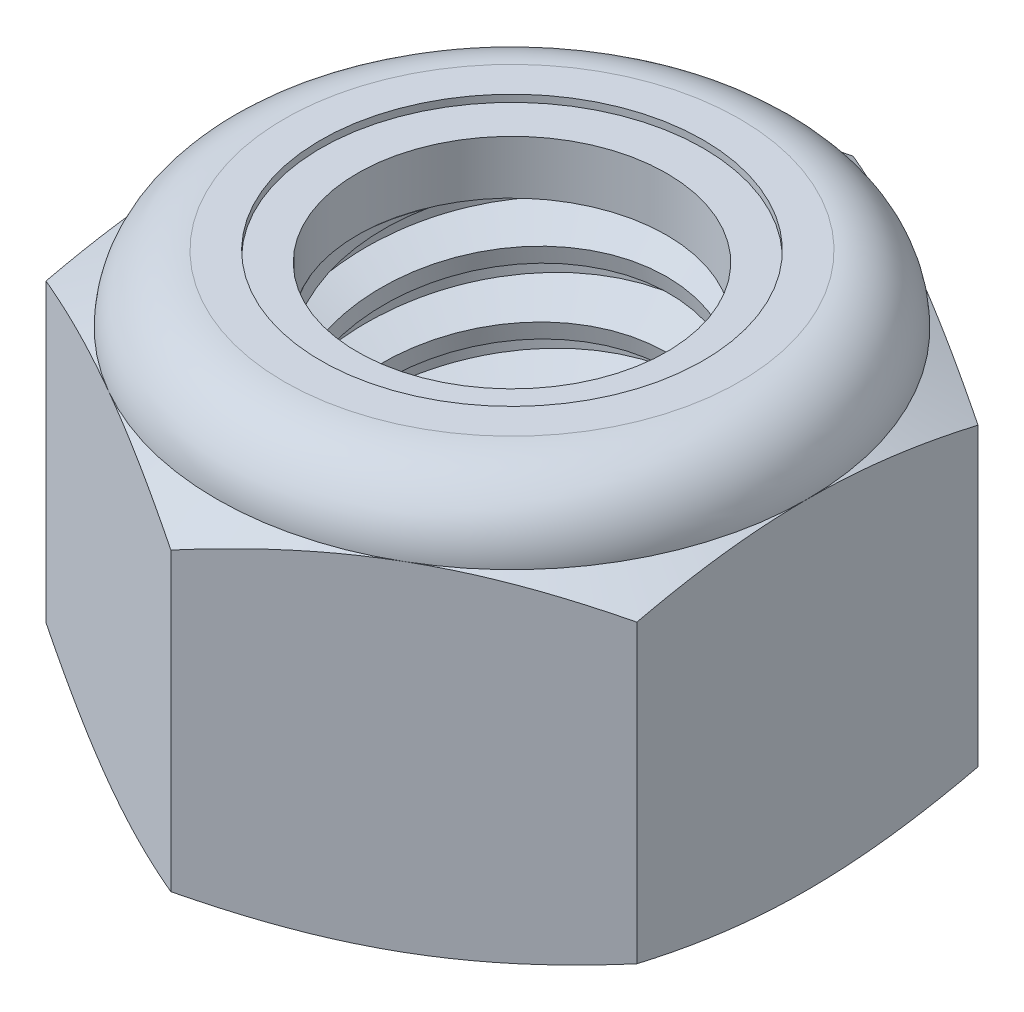
SolidWorks part; units mm, degrees
material "Plain Carbon Steel"
ref_plane "Front" through (0, 0, 0) normal (0, 0, 1) x (1, 0, 0)
ref_plane "Top" through (0, 0, 0) normal (0, 1, 0) x (1, 0, 0)
ref_plane "Right" through (0, 0, 0) normal (1, 0, 0) x (0, 0, -1)
sketch "Sketch1" plane through (0, 0, 0) normal (0, 1, 0) x (1, 0, 0)
  line L1 (0, 7.3323) -> (-6.35, 3.6662)
  line L2 (-6.35, 3.6662) -> (-6.35, -3.6662)
  line L3 (-6.35, -3.6662) -> (0, -7.3323)
  line L4 (0, -7.3323) -> (6.35, -3.6662)
  line L5 (6.35, -3.6662) -> (6.35, 3.6662)
  line L6 (6.35, 3.6662) -> (0, 7.3323)
  circle A0 centre (0, 0) radius 6.35 construction
  dimension "Hex Flats" = 12.7
extrude "Extrude1" add sketch "Sketch1" along normal blind 8.7312
sketch "Sketch2" plane through (0, 0, 0) normal (1, 0, 0) x (0, 0, -1)
  line L0 (-3.9688, 0) -> (-3.9688, 8.7312) construction
  line L1 (0, 0) -> (3.9688, 0)
  line L2 (0, 0) -> (0, 8.7312)
  line L3 (0, 8.7312) -> (3.9688, 8.7312)
  line L4 (3.9688, 0) -> (3.9688, 8.7312)
  line L5 (-3.6662, 8.7312) -> (3.6662, 8.7312) construction
  line L7 (0, -3.9688) -> (0, 0) construction
  dimension "Thread Dia" = 7.9375
revolve "Revolve1" add sketch "Sketch2" angle 360 about L7
sketch "Sketch3" plane through (0, 0, 0) normal (1, 0, 0) x (0, 0, -1)
  line L0 (3.9688, 8.7312) -> (-3.9687, 8.7312) construction
  line L1 (-3.9687, 8.7312) -> (-3.9688, 7.3201) construction
  line L2 (-3.9688, 7.3201) -> (3.9688, 8.7312) construction
  line L3 (3.9688, 8.7312) -> (3.9996, 8.5576) construction
  line L4 (3.9996, 8.5576) -> (4.2157, 7.3419)
  line L5 (4.2157, 7.3419) -> (3.3866, 7.6424)
  line L6 (3.3866, 7.6424) -> (3.3248, 7.9897)
  line L7 (3.3248, 7.9897) -> (3.9996, 8.5576)
  line L8 (3.3557, 7.8161) -> (4.1077, 7.9498) construction
  line L9 (3.9688, 8.7312) -> (3.9688, 7.9251) construction
  line L10 (3.9688, 7.9251) -> (-3.9688, 6.5139) construction
  line L11 (-3.9688, 6.5139) -> (-3.9688, 7.3201) construction
  line L12 (-0.2688, 8.7312) -> (0.2688, 5.7077) construction
  line L13 (-3.9688, 0) -> (-3.9688, 8.7312) construction
  line L14 (0, 8.7312) -> (3.9688, 8.7312) construction
  line L15 (3.9688, 0) -> (3.9688, 8.7312) construction
  point P13 (0, 7.2195)
  dimension "D1" = 0.1764
  dimension "D2" = 0.3528
  dimension "Thread Pitch" = 1.4111
  dimension "D4" = 60
  dimension "D5" = 1.4111
revolve "Cut-Revolve1" cut sketch "Sketch3" angle 360 about L12
pattern_linear "LPattern1" count 6 spacing 1.4111 along (0, -1, 0) count 2 spacing 1.4111 along (0, 1, 0) of "Cut-Revolve1"
sketch "Sketch4" plane through (0, 0, 0) normal (1, 0, 0) x (0, 0, -1)
  line L0 (0, 8.7312) -> (3.9688, 8.7312)
  line L1 (3.9688, 8.7312) -> (3.3248, 8.431)
  line L2 (3.3248, 8.431) -> (3.3248, 0.3003)
  line L3 (3.3248, 0.3003) -> (3.9688, 0)
  line L4 (3.9688, 0) -> (0, 0)
  line L5 (0, 0) -> (0, 8.7312)
  line L6 (3.9688, 0) -> (3.9688, 8.7312) construction
  line L7 (0, 8.7312) -> (3.9688, 8.7312) construction
  line L8 (0, 0) -> (3.9688, 0) construction
  line L9 (0, 0) -> (0, 8.7312) construction
  line L10 (0, 8.7312) -> (0, 9.4418) construction
  dimension "D1" = 25
revolve "Cut-Revolve2" cut sketch "Sketch4" angle 360 about L10
combine bodies "Combine1" operation type subtract main body 112 bodies to subtract 111
sketch "Sketch5" plane through (0, 0, 0) normal (1, 0, 0) x (0, 0, -1)
  line L0 (0, 0) -> (6.35, 0)
  line L1 (6.35, 0) -> (7.3323, 0.4581)
  line L2 (7.3323, 0.4581) -> (7.3323, 6.818)
  line L3 (7.3323, 6.818) -> (6.35, 7.276)
  line L4 (4.8948, 8.7312) -> (4.8948, 10.0012)
  line L5 (4.8948, 10.0012) -> (8.6023, 10.0012)
  line L6 (8.6023, 10.0012) -> (8.6023, -1.27)
  line L7 (8.6023, -1.27) -> (0, -1.27)
  line L8 (0, -1.27) -> (0, 0)
  line L9 (6.35, 7.276) -> (6.35, 0) construction
  line L10 (0, 0) -> (3.9688, 0) construction
  line L13 (7.3323, 3.638) -> (8.6023, 3.638) construction
  line L14 (7.3323, 8.7312) -> (7.3323, 0) construction
  line L15 (0, 0) -> (0, 10.0012) construction
  line L20 (0, 10.0012) -> (4.8948, 10.0012) construction
  line L22 (0, 8.7312) -> (3.9688, 8.7312) construction
  arc A0 (6.35, 7.276) -> (4.8948, 8.7312) centre (4.8948, 7.276) ccw
  dimension "D1" = 25
  dimension "D2" = 1.27
  dimension "D3" = 8.7312
  dimension "D4" = 1.4552
revolve "Cut-Revolve3" cut sketch "Sketch5" angle 360 about L15
sketch "Sketch6" plane through (0, 0, 0) normal (1, 0, 0) x (0, 0, -1)
  line L0 (0, 7.276) -> (6.1976, 7.276)
  line L1 (4.8948, 8.5788) -> (4.1098, 8.5788)
  line L2 (0, 10.0012) -> (0, 7.276)
  line L3 (4.1098, 10.0012) -> (0, 10.0012)
  line L4 (0, 10.0012) -> (4.8948, 10.0012) construction
  line L5 (0, 0) -> (0, 10.0012) construction
  line L6 (0, 10.0012) -> (0, 44.323) construction
  line L7 (4.1098, 8.5788) -> (4.1098, 10.0012)
  line L8 (4.8948, 8.7312) -> (4.8948, 8.5788) construction
  line L9 (4.1098, 8.5788) -> (3.3248, 8.5788) construction
  line L10 (3.3248, 8.5788) -> (3.3248, 8.431) construction
  arc A0 (6.1976, 7.276) -> (4.8948, 8.5788) centre (4.8948, 7.276) ccw
  arc A1 (6.35, 7.276) -> (4.8948, 8.7312) centre (4.8948, 7.276) ccw construction
  dimension "D1" = 0.1524
revolve "Cut-Revolve4" cut sketch "Sketch6" angle 360 about L6
sketch "Sketch7" plane through (0, 0, 0) normal (1, 0, 0) x (0, 0, -1)
  line L0 (3.3248, 7.3522) -> (6.119, 7.3522)
  line L1 (4.8948, 8.5027) -> (3.3248, 8.5027)
  line L2 (3.3248, 8.5027) -> (3.3248, 7.3522)
  line L3 (3.3248, 7.3522) -> (0, 7.3522) construction
  line L4 (0, 7.3522) -> (0, 8.5027) construction
  line L5 (0, 8.5027) -> (3.3248, 8.5027) construction
  line L6 (3.3248, 7.3522) -> (3.3248, 7.276) construction
  line L7 (0, 7.276) -> (6.1976, 7.276) construction
  line L8 (4.8948, 8.5027) -> (4.8948, 8.5788) construction
  arc A0 (6.119, 7.3522) -> (4.8948, 8.5027) centre (4.8948, 7.276) ccw
  arc A2 (6.1976, 7.276) -> (4.8948, 8.5788) centre (4.8948, 7.276) ccw construction
  dimension "D1" = 0.0762
revolve "Revolve2" add sketch "Sketch7" angle 360 about L4
equation "\"D1@Sketch3\"=\"Thread Pitch@Sketch3\"/8"
equation "\"D2@Sketch3\"=\"Thread Pitch@Sketch3\"/4"
equation "\"D5@Sketch3\"=\"Thread Pitch@Sketch3\""
equation "\"D4@LPattern1\"=\"Thread Pitch@Sketch3\""
equation "\"D3@LPattern1\"=\"Thread Pitch@Sketch3\""
equation "\"D1@LPattern1\"=\"Height@Extrude1\"/\"Thread Pitch@Sketch3\""
equation "\"D4@Sketch5\"=\"Height@Extrude1\"/6"
